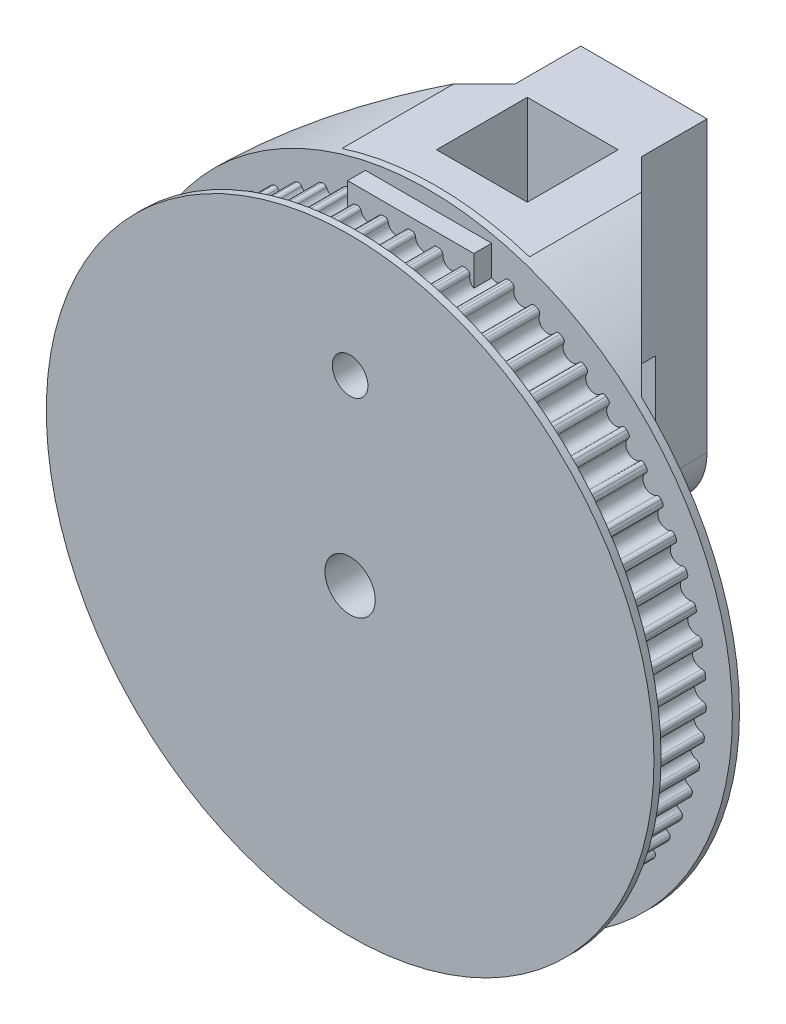
SolidWorks part; units mm, degrees
other "Markup1"
sketch "Sketch12" plane through (-30, -58, 49.7) normal (-0.8709, -0.4905, 0.0319) x (-0.1533, 0.2093, -0.9658)
other "Markup2"
sketch "Sketch14" plane through (30, -60, 49.7) normal (0.6168, -0.7172, 0.3243) x (-0.4689, -0.0038, 0.8832)
material "PETG"
ref_plane "Front Plane" through (0, 0, 0) normal (0, 0, 1) x (1, 0, 0)
ref_plane "Top Plane" through (0, 0, 0) normal (0, 1, 0) x (1, 0, 0)
ref_plane "Right Plane" through (0, 0, 0) normal (1, 0, 0) x (0, 0, -1)
sketch "Sketch1" plane through (0, 0, 0) normal (0, 1, 0) x (1, 0, 0)
  line L1 (-12.7375, -12.7375) -> (12.7375, -12.7375)
  line L2 (-12.7375, -12.7375) -> (-12.7375, 12.7375)
  line L3 (-12.7375, 12.7375) -> (12.7375, 12.7375)
  line L4 (12.7375, -12.7375) -> (12.7375, 12.7375)
  line L5 (-17.7, -17.7) -> (17.7, -17.7)
  line L6 (-17.7, -17.7) -> (-17.7, 17.7)
  line L7 (-17.7, 17.7) -> (17.7, 17.7)
  line L8 (17.7, -17.7) -> (17.7, 17.7)
  point P8 (0, -17.7)
  point P9 (0, -12.7375)
  point P12 (-17.7, 0)
  point P13 (-12.7375, 0)
  dimension "D1" = 25.475
  dimension "D2" = 35.4
extrude "Boss-Extrude1" add sketch "Sketch1" along normal blind 47.0375
extrude "Boss-Extrude2" add sketch "Sketch1<3>" against normal blind 14.9625 contours L1 L4 L3 L2 | L5 L8 L7 L6 L4 L1 L2 L3 region at (0, 0, 0) region at (-17.1994, 0, 0)
sketch "Sketch1<3>" plane through (0, 0, 0) normal (0, 1, 0) x (1, 0, 0) same geometry as "Sketch1"
sketch "Sketch3" plane through (0, 0, 0) normal (0, -1, 0) x (-1, 0, 0)
  circle A0 centre (0, 0) radius 3.15
  dimension "D1" = 6.3
extrude "Cut-Extrude1" cut sketch "Sketch3" along normal through all
sketch "Sketch13" plane through (0, -14.9625, 0) normal (0, -1, 0) x (1, 0, 0)
  circle A0 centre (0, 0) radius 5.5
  dimension "D1" = 11
extrude "Cut-Extrude4" cut sketch "Sketch13" against normal offset from surface (6.9625 mm away) 8 up to face at (0, 0, -3.15)
sketch "Sketch4" plane through (0, 0, 17.7) normal (0, 0, 1) x (1, 0, 0)
  line L0 (17.7, 47.0375) -> (17.7, -14.9625) construction
  line L1 (-17.7, 47.0375) -> (-17.7, -14.9625) construction
  line L2 (17.7, -34.0125) -> (17.7, -14.9625)
  line L3 (-17.7, -34.0125) -> (-17.7, -14.9625)
  line L5 (17.7, 47.0375) -> (-17.7, 47.0375)
  line L6 (17.7, 47.0375) -> (17.7, -14.9625)
  line L8 (-17.7, 47.0375) -> (-17.7, -14.9625)
  line L9 (-17.7, -14.9625) -> (17.7, -14.9625) construction
  line L10 (-17.7, 47.0375) -> (17.7, 47.0375) construction
  arc A0 (-17.7, -34.0125) -> (17.7, -34.0125) centre (0, -34.0125) ccw
  circle A1 centre (0, -34.0125) radius 7.05
  dimension "D2" = 14.1
  dimension "D1" = 19.05
extrude "Boss-Extrude3" add sketch "Sketch4" along normal blind 15
sketch "Sketch6" plane through (0, 0, 17.7) normal (0, 0, -1) x (-1, 0, 0)
  line L0 (17.7, -34.0125) -> (17.7, -14.9625)
  line L1 (17.7, -14.9625) -> (-17.7, -14.9625)
  line L2 (-17.7, -14.9625) -> (-17.7, -34.0125)
  arc A0 (-17.7, -34.0125) -> (17.7, -34.0125) centre (0, -34.0125) ccw
  arc A4 (-17.7, -34.0125) -> (17.7, -34.0125) centre (0, -34.0125) ccw construction
extrude "Cut-Extrude2" cut sketch "Sketch6" against normal blind 0.5375
sketch "Sketch7" plane through (0, 0, 18.2375) normal (0, 0, -1) x (-1, 0, 0)
  circle A0 centre (0, -34.0125) radius 11.0375
  arc A1 (-17.7, -34.0125) -> (17.7, -34.0125) centre (0, -34.0125) ccw construction
  dimension "D1" = 22.075
extrude "Cut-Extrude3" cut sketch "Sketch7" against normal blind 7
mirror "Mirror1" about plane through (0, 0, 0) normal (0, 0, 1) of "Boss-Extrude3", "Cut-Extrude2", "Cut-Extrude1", "Cut-Extrude3"
sketch "Sketch18" plane through (0, 0, 0) normal (0, 0, 1) x (1, 0, 0)
  line L0 (0, -13.5166) -> (-17.7, -3.2975)
  line L1 (-17.7, -3.2975) -> (-35.45, -34.0414) construction
  line L2 (-35.45, -34.0414) -> (-8.875, -49.3845) construction
  line L3 (-17.7, 47.0375) -> (-17.7, -34.0125) construction
  line L4 (0, -35.0322) -> (0, -50035.0322) construction
  line L5 (-17.7, -3.2975) -> (-17.7, -14.9625)
  line L6 (17.7, -34.0125) -> (17.7, 47.0375) construction
  line L7 (17.7, -3.2975) -> (0, -13.5166)
  line L10 (17.7, -14.9625) -> (17.7, -3.2975)
  line L11 (-17.7, -14.9625) -> (17.7, -14.9625)
  line L12 (-5.5, -14.9625) -> (5.5, -14.9625) construction
  circle A0 centre (0, -34.0125) radius 17.75 construction
  arc A2 (-17.7, -34.0125) -> (17.7, -34.0125) centre (0, -34.0125) ccw construction
  dimension "D2" = 120
  dimension "D1" = 35.5
extrude "Cut-Extrude10" cut sketch "Sketch18" along normal up to surface and the other way up to surface up to face at (-11.0375, -34.0125, 18.2375) other way up to face at (-11.0375, -34.0125, -18.2375)
ref_plane "Plane1" through (0, 0, 27.7) normal (0, 0, 1) x (1, 0, 0)
sketch "Sketch9" plane through (0, 0, 27.7) normal (0, 0, 1) x (1, 0, 0)
  circle A0 centre (0, -34.0125) radius 85.2141
  circle A1 centre (0, -34.0125) radius 7.05 construction
  circle A2 centre (0, -34.0125) radius 7.05
  dimension "D1" = 170.4282
extrude "Boss-Extrude4" add sketch "Sketch9" against normal blind 2 contours A0 region at (-82.8039, -34.0125, 27.7)
sketch "Sketch10" plane through (0, 0, 27.7) normal (0, 0, -1) x (-1, 0, 0)
  line L0 (0, -41.0625) -> (0, -50041.0625) construction
  line L1 (0, -34.0125) -> (-3.9983, -114.1269) construction
  line L2 (0, -34.0125) -> (3.9983, -114.1269) construction
  circle A0 centre (0, -34.0125) radius 80.2141 construction
  circle A1 centre (0, -34.0125) radius 7.05
  circle A2 centre (0, -34.0125) radius 85.2141 construction
  circle A3 centre (0, -34.0125) radius 7.05 construction
  arc A4 (2.4815, -110.9206) -> (-2.4815, -110.9206) centre (0, -111.1266) ccw
  arc A5 (-3.5233, -111.8369) -> (-2.4815, -110.9206) centre (-3.478, -110.8379) ccw
  circle A6 centre (0, -34.0125) radius 77.9041 construction
  arc A7 (2.4815, -110.9206) -> (3.5233, -111.8369) centre (3.478, -110.8379) ccw
  arc A8 (3.5233, -111.8369) -> (3.8832, -111.8198) centre (0, -34.0125) ccw
  arc A9 (-3.8832, -111.8198) -> (-3.5233, -111.8369) centre (0, -34.0125) ccw
  arc A10 (-11.611, -111.0465) -> (-11.2546, -111.0993) centre (0, -34.0125) ccw
  arc A11 (-11.2546, -111.0993) -> (-10.1267, -110.2914) centre (-11.1101, -110.1098) ccw
  arc A12 (-5.1884, -110.7855) -> (-10.1267, -110.2914) centre (-7.6781, -110.7434) ccw
  arc A13 (-5.1884, -110.7855) -> (-4.243, -111.801) centre (-4.1886, -110.8024) ccw
  arc A14 (-4.243, -111.801) -> (-3.8832, -111.8198) centre (0, -34.0125) ccw
  arc A15 (-19.2234, -109.5076) -> (-18.874, -109.5957) centre (0, -34.0125) ccw
  arc A16 (-18.874, -109.5957) -> (-17.6713, -108.904) centre (-18.6317, -108.6255) ccw
  arc A17 (-12.8068, -109.8874) -> (-17.6713, -108.904) centre (-15.2799, -109.5976) ccw
  arc A18 (-12.8068, -109.8874) -> (-11.9672, -110.9919) centre (-11.8136, -110.0038) ccw
  arc A19 (-11.9672, -110.9919) -> (-11.611, -111.0465) centre (0, -34.0125) ccw
  arc A20 (-26.6448, -107.2184) -> (-26.3059, -107.3409) centre (0, -34.0125) ccw
  arc A21 (-26.3059, -107.3409) -> (-25.0403, -106.7724) centre (-25.9682, -106.3996) ccw
  arc A22 (-20.2978, -108.2352) -> (-25.0403, -106.7724) centre (-22.7298, -107.7006) ccw
  arc A23 (-20.2978, -108.2352) -> (-19.5724, -109.4179) centre (-19.3212, -108.4499) ccw
  arc A24 (-19.5724, -109.4179) -> (-19.2234, -109.5076) centre (0, -34.0125) ccw
  arc A25 (-33.8013, -104.2017) -> (-33.4763, -104.3573) centre (0, -34.0125) ccw
  arc A26 (-33.4763, -104.3573) -> (-32.1604, -103.9176) centre (-33.0466, -103.4543) ccw
  arc A27 (-27.5872, -105.8454) -> (-32.1604, -103.9176) centre (-29.9538, -105.0713) ccw
  arc A28 (-27.5872, -105.8454) -> (-26.9831, -107.0944) centre (-26.6367, -106.1563) ccw
  arc A29 (-26.9831, -107.0944) -> (-26.6448, -107.2184) centre (0, -34.0125) ccw
  arc A30 (-40.6219, -100.4874) -> (-40.314, -100.6745) centre (0, -34.0125) ccw
  arc A31 (-40.314, -100.6745) -> (-38.9609, -100.3681) centre (-39.7965, -99.8188) ccw
  arc A32 (-34.6023, -102.7416) -> (-38.9609, -100.3681) centre (-36.8801, -101.7358) ccw
  arc A33 (-34.6023, -102.7416) -> (-34.1256, -104.0446) centre (-33.6876, -103.1456) ccw
  arc A34 (-34.1256, -104.0446) -> (-33.8013, -104.2017) centre (0, -34.0125) ccw
  arc A35 (-47.0388, -96.1124) -> (-46.7511, -96.3293) centre (0, -34.0125) ccw
  arc A36 (-46.7511, -96.3293) -> (-45.3742, -96.1591) centre (-46.151, -95.5294) ccw
  arc A37 (-41.2736, -98.9548) -> (-45.3742, -96.1591) centre (-43.4399, -97.7272) ccw
  arc A38 (-41.2736, -98.9548) -> (-40.929, -100.2987) centre (-40.4036, -99.4479) ccw
  arc A39 (-40.929, -100.2987) -> (-40.6219, -100.4874) centre (0, -34.0125) ccw
  arc A40 (-52.9882, -91.1202) -> (-52.7235, -91.3647) centre (0, -34.0125) ccw
  arc A41 (-52.7235, -91.3647) -> (-51.3365, -91.3325) centre (-52.0467, -90.6285) ccw
  arc A42 (-47.5347, -94.5226) -> (-51.3365, -91.3325) centre (-49.568, -93.0853) ccw
  arc A43 (-47.5347, -94.5226) -> (-47.3256, -95.8941) centre (-46.7181, -95.0998) ccw
  arc A44 (-47.3256, -95.8941) -> (-47.0388, -96.1124) centre (0, -34.0125) ccw
  arc A45 (-58.411, -85.5605) -> (-58.172, -85.8302) centre (0, -34.0125) ccw
  arc A46 (-58.172, -85.8302) -> (-56.7886, -85.9362) centre (-57.4253, -85.165) ccw
  arc A47 (-53.3233, -89.489) -> (-56.7886, -85.9362) centre (-55.2034, -87.8564) ccw
  arc A48 (-53.3233, -89.489) -> (-53.2518, -90.8745) centre (-52.5683, -90.1446) ccw
  arc A49 (-53.2518, -90.8745) -> (-52.9882, -91.1202) centre (0, -34.0125) ccw
  arc A50 (-63.2533, -79.4885) -> (-63.0423, -79.7806) centre (0, -34.0125) ccw
  arc A51 (-63.0423, -79.7806) -> (-61.6764, -80.0238) centre (-62.233, -79.1931) ccw
  arc A52 (-58.582, -83.904) -> (-61.6764, -80.0238) centre (-60.2902, -82.0923) ccw
  arc A53 (-58.582, -83.904) -> (-58.6488, -85.2898) centre (-57.896, -84.6316) ccw
  arc A54 (-58.6488, -85.2898) -> (-58.411, -85.5605) centre (0, -34.0125) ccw
  arc A55 (-67.4669, -72.9645) -> (-67.286, -73.2762) centre (0, -34.0125) ccw
  arc A56 (-67.286, -73.2762) -> (-65.9511, -73.6542) centre (-66.4223, -72.7722) ccw
  arc A57 (-63.2585, -77.8232) -> (-65.9511, -73.6542) centre (-64.7778, -75.8505) ccw
  arc A58 (-63.2585, -77.8232) -> (-63.463, -79.1955) centre (-62.6483, -78.6155) ccw
  arc A59 (-63.463, -79.1955) -> (-63.2533, -79.4885) centre (0, -34.0125) ccw
  arc A60 (-71.01, -66.0534) -> (-70.8611, -66.3816) centre (0, -34.0125) ccw
  arc A61 (-70.8611, -66.3816) -> (-69.5704, -66.8906) centre (-69.9515, -65.9661) ccw
  arc A62 (-67.3063, -71.307) -> (-69.5704, -66.8906) centre (-68.6217, -69.1928) ccw
  arc A63 (-67.3063, -71.307) -> (-67.6464, -72.6521) centre (-66.778, -72.1561) ccw
  arc A64 (-67.6464, -72.6521) -> (-67.4669, -72.9645) centre (0, -34.0125) ccw
  arc A65 (-73.8474, -58.8239) -> (-73.7319, -59.1652) centre (0, -34.0125) ccw
  arc A66 (-73.7319, -59.1652) -> (-72.4983, -59.8003) centre (-72.7854, -58.8424) ccw
  arc A67 (-70.6852, -64.4201) -> (-72.4983, -59.8003) centre (-71.7835, -62.1854) ccw
  arc A68 (-70.6852, -64.4201) -> (-71.1575, -65.7247) centre (-70.2441, -65.3176) ccw
  arc A69 (-71.1575, -65.7247) -> (-71.01, -66.0534) centre (0, -34.0125) ccw
  arc A70 (-75.9509, -51.3478) -> (-75.8699, -51.6989) centre (0, -34.0125) ccw
  arc A71 (-75.8699, -51.6989) -> (-74.7057, -52.4536) centre (-74.896, -51.4719) ccw
  arc A72 (-73.3615, -57.2311) -> (-74.7057, -52.4536) centre (-74.2319, -54.8981) ccw
  arc A73 (-73.3615, -57.2311) -> (-73.9614, -58.4821) centre (-73.012, -58.168) ccw
  arc A74 (-73.9614, -58.4821) -> (-73.8474, -58.8239) centre (0, -34.0125) ccw
  arc A75 (-77.2995, -43.6994) -> (-77.2539, -44.0568) centre (0, -34.0125) ccw
  arc A76 (-77.2539, -44.0568) -> (-76.1706, -44.9237) centre (-76.2622, -43.9279) ccw
  arc A77 (-75.3088, -49.8112) -> (-76.1706, -44.9237) centre (-75.9426, -47.4032) ccw
  arc A78 (-75.3088, -49.8112) -> (-76.0302, -50.9963) centre (-75.0543, -50.7783) ccw
  arc A79 (-76.0302, -50.9963) -> (-75.9509, -51.3478) centre (0, -34.0125) ccw
  arc A80 (-77.8799, -35.9547) -> (-77.8701, -36.3149) centre (0, -34.0125) ccw
  arc A81 (-77.8701, -36.3149) -> (-76.8785, -37.2853) centre (-76.8705, -36.2854) ccw
  arc A82 (-76.5076, -42.2344) -> (-76.8785, -37.2853) centre (-76.8985, -39.7752) ccw
  arc A83 (-76.5076, -42.2344) -> (-77.3435, -43.3417) centre (-76.3507, -43.222) ccw
  arc A84 (-77.3435, -43.3417) -> (-77.2995, -43.6994) centre (0, -34.0125) ccw
  arc A85 (-77.6863, -28.1907) -> (-77.7124, -28.5501) centre (0, -34.0125) ccw
  arc A86 (-77.7124, -28.5501) -> (-76.8224, -29.6144) centre (-76.7148, -28.6202) ccw
  arc A87 (-76.9461, -34.5758) -> (-76.8224, -29.6144) centre (-77.0901, -32.09) ccw
  arc A88 (-76.9461, -34.5758) -> (-77.888, -35.5945) centre (-76.8882, -35.5741) ccw
  arc A89 (-77.888, -35.5945) -> (-77.8799, -35.9547) centre (0, -34.0125) ccw
  arc A90 (-76.7206, -20.4846) -> (-76.7823, -20.8396) centre (0, -34.0125) ccw
  arc A91 (-76.7823, -20.8396) -> (-76.0027, -21.9873) centre (-75.7967, -21.0087) ccw
  arc A92 (-76.6198, -26.9117) -> (-76.0027, -21.9873) centre (-76.5156, -24.4238) ccw
  arc A93 (-76.6198, -26.9117) -> (-77.6585, -27.8315) centre (-76.6616, -27.9108) ccw
  arc A94 (-77.6585, -27.8315) -> (-77.6863, -28.1907) centre (0, -34.0125) ccw
  arc A95 (-74.9924, -12.9129) -> (-75.0892, -13.26) centre (0, -34.0125) ccw
  arc A96 (-75.0892, -13.26) -> (-74.4277, -14.4796) centre (-74.1253, -13.5264) ccw
  arc A97 (-75.5321, -19.3181) -> (-74.4277, -14.4796) centre (-75.1807, -16.853) ccw
  arc A98 (-75.5321, -19.3181) -> (-76.6572, -20.1299) centre (-75.6732, -20.3081) ccw
  arc A99 (-76.6572, -20.1299) -> (-76.7206, -20.4846) centre (0, -34.0125) ccw
  arc A100 (-72.5189, -5.5509) -> (-72.6497, -5.8867) centre (0, -34.0125) ccw
  arc A101 (-72.6497, -5.8867) -> (-72.113, -7.166) centre (-71.7172, -6.2477) ccw
  arc A102 (-73.6936, -11.8705) -> (-72.113, -7.166) centre (-73.0986, -9.4527) ccw
  arc A103 (-73.6936, -11.8705) -> (-74.894, -12.5663) centre (-73.9326, -12.8416) ccw
  arc A104 (-74.894, -12.5663) -> (-74.9924, -12.9129) centre (0, -34.0125) ccw
  arc A105 (-69.3247, 1.5282) -> (-69.4883, 1.2071) centre (0, -34.0125) ccw
  arc A106 (-69.4883, 1.2071) -> (-69.0816, -0.1193) centre (-68.5963, 0.7551) ccw
  arc A107 (-71.1228, -4.6431) -> (-69.0816, -0.1193) centre (-70.2899, -2.2965) ccw
  arc A108 (-71.1228, -4.6431) -> (-72.3865, -5.2158) centre (-71.4573, -5.5855) ccw
  arc A109 (-72.3865, -5.2158) -> (-72.5189, -5.5509) centre (0, -34.0125) ccw
  arc A110 (-65.4415, 8.2541) -> (-65.6363, 7.9509) centre (0, -34.0125) ccw
  arc A111 (-65.6363, 7.9509) -> (-65.3637, 6.5906) centre (-64.7937, 7.4123) ccw
  arc A112 (-67.8451, 2.2925) -> (-65.3637, 6.5906) centre (-66.7828, 4.5445) ccw
  arc A113 (-67.8451, 2.2925) -> (-69.1595, 1.8485) centre (-68.2718, 1.3881) ccw
  arc A114 (-69.1595, 1.8485) -> (-69.3247, 1.5282) centre (0, -34.0125) ccw
  arc A115 (-60.9079, 14.5599) -> (-61.1319, 14.2777) centre (0, -34.0125) ccw
  arc A116 (-61.1319, 14.2777) -> (-60.9961, 12.8969) centre (-60.3472, 13.6578) ccw
  arc A117 (-63.8932, 8.8673) -> (-60.9961, 12.8969) centre (-62.6119, 11.0024) ccw
  arc A118 (-63.8932, 8.8673) -> (-65.2453, 8.5563) centre (-64.4077, 8.0099) ccw
  arc A119 (-65.2453, 8.5563) -> (-65.4415, 8.2541) centre (0, -34.0125) ccw
  arc A120 (-55.769, 20.383) -> (-56.02, 20.1245) centre (0, -34.0125) ccw
  arc A121 (-56.02, 20.1245) -> (-56.0223, 18.7371) centre (-55.3009, 19.4295) ccw
  arc A122 (-59.3062, 15.016) -> (-56.0223, 18.7371) centre (-57.8187, 17.0128) ccw
  arc A123 (-59.3062, 15.016) -> (-60.6826, 14.8411) centre (-59.9036, 14.214) ccw
  arc A124 (-60.6826, 14.8411) -> (-60.9079, 14.5599) centre (0, -34.0125) ccw
  arc A125 (-50.0758, 25.6655) -> (-50.3513, 25.4332) centre (0, -34.0125) ccw
  arc A126 (-50.3513, 25.4332) -> (-50.4918, 24.053) centre (-49.705, 24.6702) ccw
  arc A127 (-54.1299, 20.6773) -> (-50.4918, 24.053) centre (-52.4509, 22.5161) ccw
  arc A128 (-54.1299, 20.6773) -> (-55.5168, 20.6404) centre (-54.8041, 19.9388) ccw
  arc A129 (-55.5168, 20.6404) -> (-55.769, 20.383) centre (0, -34.0125) ccw
  arc A130 (-43.8849, 30.3549) -> (-44.1822, 30.1512) centre (0, -34.0125) ccw
  arc A131 (-44.1822, 30.1512) -> (-44.4594, 28.7918) centre (-43.6151, 29.3276) ccw
  arc A132 (-48.4155, 25.7951) -> (-44.4594, 28.7918) centre (-46.5618, 27.4576) ccw
  arc A133 (-48.4155, 25.7951) -> (-49.7992, 25.8965) centre (-49.16, 25.1275) ccw
  arc A134 (-49.7992, 25.8965) -> (-50.0758, 25.6655) centre (0, -34.0125) ccw
  arc A135 (-37.2579, 34.4046) -> (-37.574, 34.2315) centre (0, -34.0125) ccw
  arc A136 (-37.574, 34.2315) -> (-37.9852, 32.9064) centre (-37.0917, 33.3555) ccw
  arc A137 (-42.22, 30.3186) -> (-37.9852, 32.9064) centre (-40.21, 31.7883) ccw
  arc A138 (-42.22, 30.3186) -> (-43.5867, 30.5572) centre (-43.0272, 29.7283) ccw
  arc A139 (-43.5867, 30.5572) -> (-43.8849, 30.3549) centre (0, -34.0125) ccw
  arc A140 (-30.2607, 37.7743) -> (-30.5924, 37.6335) centre (0, -34.0125) ccw
  arc A141 (-30.5924, 37.6335) -> (-31.1335, 36.356) centre (-30.1997, 36.7139) ccw
  arc A142 (-35.6049, 34.2027) -> (-31.1335, 36.356) centre (-33.4586, 35.4649) ccw
  arc A143 (-35.6049, 34.2027) -> (-36.9411, 34.5762) centre (-36.4669, 33.6957) ccw
  arc A144 (-36.9411, 34.5762) -> (-37.2579, 34.4046) centre (0, -34.0125) ccw
  arc A145 (-22.9626, 40.4305) -> (-23.3067, 40.3235) centre (0, -34.0125) ccw
  arc A146 (-23.3067, 40.3235) -> (-23.9723, 39.1062) centre (-23.0075, 39.3693) ccw
  arc A147 (-28.6359, 37.4088) -> (-23.9723, 39.1062) centre (-26.3746, 38.451) ccw
  arc A148 (-28.6359, 37.4088) -> (-29.9283, 37.9135) centre (-29.5441, 36.9902) ccw
  arc A149 (-29.9283, 37.9135) -> (-30.2607, 37.7743) centre (0, -34.0125) ccw
  arc A150 (-15.4364, 42.3469) -> (-15.7894, 42.2747) centre (0, -34.0125) ccw
  arc A151 (-15.7894, 42.2747) -> (-16.5729, 41.1297) centre (-15.5867, 41.2955) ccw
  arc A152 (-21.3824, 39.9051) -> (-16.5729, 41.1297) centre (-19.0285, 40.717) ccw
  arc A153 (-21.3824, 39.9051) -> (-22.6181, 40.5359) centre (-22.3277, 39.579) ccw
  arc A154 (-22.6181, 40.5359) -> (-22.9626, 40.4305) centre (0, -34.0125) ccw
  arc A155 (-7.7567, 43.5045) -> (-8.1152, 43.4678) centre (0, -34.0125) ccw
  arc A156 (-8.1152, 43.4678) -> (-9.0088, 42.4065) centre (-8.011, 42.4732) ccw
  arc A157 (-13.9163, 41.6668) -> (-9.0088, 42.4065) centre (-11.4933, 42.2403) ccw
  arc A158 (-13.9163, 41.6668) -> (-15.083, 42.4175) centre (-14.8894, 41.4365) ccw
  arc A159 (-15.083, 42.4175) -> (-15.4364, 42.3469) centre (0, -34.0125) ccw
  arc A160 (0, 43.8916) -> (-0.3603, 43.8908) centre (0, -34.0125) ccw
  arc A161 (-0.3603, 43.8908) -> (-1.3552, 42.9237) centre (-0.3557, 42.8908) ccw
  arc A162 (-6.3119, 42.6763) -> (-1.3552, 42.9237) centre (-3.8438, 43.0057) ccw
  arc A163 (-6.3119, 42.6763) -> (-7.3981, 43.5395) centre (-7.3031, 42.544) ccw
  arc A164 (-7.3981, 43.5395) -> (-7.7567, 43.5045) centre (0, -34.0125) ccw
  arc A165 (7.7567, 43.5045) -> (7.3981, 43.5395) centre (0, -34.0125) ccw
  arc A166 (7.3981, 43.5395) -> (6.3119, 42.6763) centre (7.3031, 42.544) ccw
  arc A167 (1.3552, 42.9237) -> (6.3119, 42.6763) centre (3.8438, 43.0057) ccw
  arc A168 (1.3552, 42.9237) -> (0.3603, 43.8908) centre (0.3557, 42.8908) ccw
  arc A169 (0.3603, 43.8908) -> (0, 43.8916) centre (0, -34.0125) ccw
  arc A170 (15.4364, 42.3469) -> (15.083, 42.4175) centre (0, -34.0125) ccw
  arc A171 (15.083, 42.4175) -> (13.9163, 41.6668) centre (14.8894, 41.4365) ccw
  arc A172 (9.0088, 42.4065) -> (13.9163, 41.6668) centre (11.4933, 42.2403) ccw
  arc A173 (9.0088, 42.4065) -> (8.1152, 43.4678) centre (8.011, 42.4732) ccw
  arc A174 (8.1152, 43.4678) -> (7.7567, 43.5045) centre (0, -34.0125) ccw
  arc A175 (22.9626, 40.4305) -> (22.6181, 40.5359) centre (0, -34.0125) ccw
  arc A176 (22.6181, 40.5359) -> (21.3824, 39.9051) centre (22.3277, 39.579) ccw
  arc A177 (16.5729, 41.1297) -> (21.3824, 39.9051) centre (19.0285, 40.717) ccw
  arc A178 (16.5729, 41.1297) -> (15.7894, 42.2747) centre (15.5867, 41.2955) ccw
  arc A179 (15.7894, 42.2747) -> (15.4364, 42.3469) centre (0, -34.0125) ccw
  arc A180 (30.2607, 37.7743) -> (29.9283, 37.9135) centre (0, -34.0125) ccw
  arc A181 (29.9283, 37.9135) -> (28.6359, 37.4088) centre (29.5441, 36.9902) ccw
  arc A182 (23.9723, 39.1062) -> (28.6359, 37.4088) centre (26.3746, 38.451) ccw
  arc A183 (23.9723, 39.1062) -> (23.3067, 40.3235) centre (23.0075, 39.3693) ccw
  arc A184 (23.3067, 40.3235) -> (22.9626, 40.4305) centre (0, -34.0125) ccw
  arc A185 (37.2579, 34.4046) -> (36.9411, 34.5762) centre (0, -34.0125) ccw
  arc A186 (36.9411, 34.5762) -> (35.6049, 34.2027) centre (36.4669, 33.6957) ccw
  arc A187 (31.1335, 36.356) -> (35.6049, 34.2027) centre (33.4586, 35.4649) ccw
  arc A188 (31.1335, 36.356) -> (30.5924, 37.6335) centre (30.1997, 36.7139) ccw
  arc A189 (30.5924, 37.6335) -> (30.2607, 37.7743) centre (0, -34.0125) ccw
  arc A190 (43.8849, 30.3549) -> (43.5867, 30.5572) centre (0, -34.0125) ccw
  arc A191 (43.5867, 30.5572) -> (42.22, 30.3186) centre (43.0272, 29.7283) ccw
  arc A192 (37.9852, 32.9064) -> (42.22, 30.3186) centre (40.21, 31.7883) ccw
  arc A193 (37.9852, 32.9064) -> (37.574, 34.2315) centre (37.0917, 33.3555) ccw
  arc A194 (37.574, 34.2315) -> (37.2579, 34.4046) centre (0, -34.0125) ccw
  arc A195 (50.0758, 25.6655) -> (49.7992, 25.8965) centre (0, -34.0125) ccw
  arc A196 (49.7992, 25.8965) -> (48.4155, 25.7951) centre (49.16, 25.1275) ccw
  arc A197 (44.4594, 28.7918) -> (48.4155, 25.7951) centre (46.5618, 27.4576) ccw
  arc A198 (44.4594, 28.7918) -> (44.1822, 30.1512) centre (43.6151, 29.3276) ccw
  arc A199 (44.1822, 30.1512) -> (43.8849, 30.3549) centre (0, -34.0125) ccw
  arc A200 (55.769, 20.383) -> (55.5168, 20.6404) centre (0, -34.0125) ccw
  arc A201 (55.5168, 20.6404) -> (54.1299, 20.6773) centre (54.8041, 19.9388) ccw
  arc A202 (50.4918, 24.053) -> (54.1299, 20.6773) centre (52.4509, 22.5161) ccw
  arc A203 (50.4918, 24.053) -> (50.3513, 25.4332) centre (49.705, 24.6702) ccw
  arc A204 (50.3513, 25.4332) -> (50.0758, 25.6655) centre (0, -34.0125) ccw
  arc A205 (60.9079, 14.5599) -> (60.6826, 14.8411) centre (0, -34.0125) ccw
  arc A206 (60.6826, 14.8411) -> (59.3062, 15.016) centre (59.9036, 14.214) ccw
  arc A207 (56.0223, 18.7371) -> (59.3062, 15.016) centre (57.8187, 17.0128) ccw
  arc A208 (56.0223, 18.7371) -> (56.02, 20.1245) centre (55.3009, 19.4295) ccw
  arc A209 (56.02, 20.1245) -> (55.769, 20.383) centre (0, -34.0125) ccw
  arc A210 (65.4415, 8.2541) -> (65.2453, 8.5563) centre (0, -34.0125) ccw
  arc A211 (65.2453, 8.5563) -> (63.8932, 8.8673) centre (64.4077, 8.0099) ccw
  arc A212 (60.9961, 12.8969) -> (63.8932, 8.8673) centre (62.6119, 11.0024) ccw
  arc A213 (60.9961, 12.8969) -> (61.1319, 14.2777) centre (60.3472, 13.6578) ccw
  arc A214 (61.1319, 14.2777) -> (60.9079, 14.5599) centre (0, -34.0125) ccw
  arc A215 (69.3247, 1.5282) -> (69.1595, 1.8485) centre (0, -34.0125) ccw
  arc A216 (69.1595, 1.8485) -> (67.8451, 2.2925) centre (68.2718, 1.3881) ccw
  arc A217 (65.3637, 6.5906) -> (67.8451, 2.2925) centre (66.7828, 4.5445) ccw
  arc A218 (65.3637, 6.5906) -> (65.6363, 7.9509) centre (64.7937, 7.4123) ccw
  arc A219 (65.6363, 7.9509) -> (65.4415, 8.2541) centre (0, -34.0125) ccw
  arc A220 (72.5189, -5.5509) -> (72.3865, -5.2158) centre (0, -34.0125) ccw
  arc A221 (72.3865, -5.2158) -> (71.1228, -4.6431) centre (71.4573, -5.5855) ccw
  arc A222 (69.0816, -0.1193) -> (71.1228, -4.6431) centre (70.2899, -2.2965) ccw
  arc A223 (69.0816, -0.1193) -> (69.4883, 1.2071) centre (68.5963, 0.7551) ccw
  arc A224 (69.4883, 1.2071) -> (69.3247, 1.5282) centre (0, -34.0125) ccw
  arc A225 (74.9924, -12.9129) -> (74.894, -12.5663) centre (0, -34.0125) ccw
  arc A226 (74.894, -12.5663) -> (73.6936, -11.8705) centre (73.9326, -12.8416) ccw
  arc A227 (72.113, -7.166) -> (73.6936, -11.8705) centre (73.0986, -9.4527) ccw
  arc A228 (72.113, -7.166) -> (72.6497, -5.8867) centre (71.7172, -6.2477) ccw
  arc A229 (72.6497, -5.8867) -> (72.5189, -5.5509) centre (0, -34.0125) ccw
  arc A230 (76.7206, -20.4846) -> (76.6572, -20.1299) centre (0, -34.0125) ccw
  arc A231 (76.6572, -20.1299) -> (75.5321, -19.3181) centre (75.6732, -20.3081) ccw
  arc A232 (74.4277, -14.4796) -> (75.5321, -19.3181) centre (75.1807, -16.853) ccw
  arc A233 (74.4277, -14.4796) -> (75.0892, -13.26) centre (74.1253, -13.5264) ccw
  arc A234 (75.0892, -13.26) -> (74.9924, -12.9129) centre (0, -34.0125) ccw
  arc A235 (77.6863, -28.1907) -> (77.6585, -27.8315) centre (0, -34.0125) ccw
  arc A236 (77.6585, -27.8315) -> (76.6198, -26.9117) centre (76.6616, -27.9108) ccw
  arc A237 (76.0027, -21.9873) -> (76.6198, -26.9117) centre (76.5156, -24.4238) ccw
  arc A238 (76.0027, -21.9873) -> (76.7823, -20.8396) centre (75.7967, -21.0087) ccw
  arc A239 (76.7823, -20.8396) -> (76.7206, -20.4846) centre (0, -34.0125) ccw
  arc A240 (77.8799, -35.9547) -> (77.888, -35.5945) centre (0, -34.0125) ccw
  arc A241 (77.888, -35.5945) -> (76.9461, -34.5758) centre (76.8882, -35.5741) ccw
  arc A242 (76.8224, -29.6144) -> (76.9461, -34.5758) centre (77.0901, -32.09) ccw
  arc A243 (76.8224, -29.6144) -> (77.7124, -28.5501) centre (76.7148, -28.6202) ccw
  arc A244 (77.7124, -28.5501) -> (77.6863, -28.1907) centre (0, -34.0125) ccw
  arc A245 (77.2995, -43.6994) -> (77.3435, -43.3417) centre (0, -34.0125) ccw
  arc A246 (77.3435, -43.3417) -> (76.5076, -42.2344) centre (76.3507, -43.222) ccw
  arc A247 (76.8785, -37.2853) -> (76.5076, -42.2344) centre (76.8985, -39.7752) ccw
  arc A248 (76.8785, -37.2853) -> (77.8701, -36.3149) centre (76.8705, -36.2854) ccw
  arc A249 (77.8701, -36.3149) -> (77.8799, -35.9547) centre (0, -34.0125) ccw
  arc A250 (75.9509, -51.3478) -> (76.0302, -50.9963) centre (0, -34.0125) ccw
  arc A251 (76.0302, -50.9963) -> (75.3088, -49.8112) centre (75.0543, -50.7783) ccw
  arc A252 (76.1706, -44.9237) -> (75.3088, -49.8112) centre (75.9426, -47.4032) ccw
  arc A253 (76.1706, -44.9237) -> (77.2539, -44.0568) centre (76.2622, -43.9279) ccw
  arc A254 (77.2539, -44.0568) -> (77.2995, -43.6994) centre (0, -34.0125) ccw
  arc A255 (73.8474, -58.8239) -> (73.9614, -58.4821) centre (0, -34.0125) ccw
  arc A256 (73.9614, -58.4821) -> (73.3615, -57.2311) centre (73.012, -58.168) ccw
  arc A257 (74.7057, -52.4536) -> (73.3615, -57.2311) centre (74.2319, -54.8981) ccw
  arc A258 (74.7057, -52.4536) -> (75.8699, -51.6989) centre (74.896, -51.4719) ccw
  arc A259 (75.8699, -51.6989) -> (75.9509, -51.3478) centre (0, -34.0125) ccw
  arc A260 (71.01, -66.0534) -> (71.1575, -65.7247) centre (0, -34.0125) ccw
  arc A261 (71.1575, -65.7247) -> (70.6852, -64.4201) centre (70.2441, -65.3176) ccw
  arc A262 (72.4983, -59.8003) -> (70.6852, -64.4201) centre (71.7835, -62.1854) ccw
  arc A263 (72.4983, -59.8003) -> (73.7319, -59.1652) centre (72.7854, -58.8424) ccw
  arc A264 (73.7319, -59.1652) -> (73.8474, -58.8239) centre (0, -34.0125) ccw
  arc A265 (67.4669, -72.9645) -> (67.6464, -72.6521) centre (0, -34.0125) ccw
  arc A266 (67.6464, -72.6521) -> (67.3063, -71.307) centre (66.778, -72.1561) ccw
  arc A267 (69.5704, -66.8906) -> (67.3063, -71.307) centre (68.6217, -69.1928) ccw
  arc A268 (69.5704, -66.8906) -> (70.8611, -66.3816) centre (69.9515, -65.9661) ccw
  arc A269 (70.8611, -66.3816) -> (71.01, -66.0534) centre (0, -34.0125) ccw
  arc A270 (63.2533, -79.4885) -> (63.463, -79.1955) centre (0, -34.0125) ccw
  arc A271 (63.463, -79.1955) -> (63.2585, -77.8232) centre (62.6483, -78.6155) ccw
  arc A272 (65.9511, -73.6542) -> (63.2585, -77.8232) centre (64.7778, -75.8505) ccw
  arc A273 (65.9511, -73.6542) -> (67.286, -73.2762) centre (66.4223, -72.7722) ccw
  arc A274 (67.286, -73.2762) -> (67.4669, -72.9645) centre (0, -34.0125) ccw
  arc A275 (58.411, -85.5605) -> (58.6488, -85.2898) centre (0, -34.0125) ccw
  arc A276 (58.6488, -85.2898) -> (58.582, -83.904) centre (57.896, -84.6316) ccw
  arc A277 (61.6764, -80.0238) -> (58.582, -83.904) centre (60.2902, -82.0923) ccw
  arc A278 (61.6764, -80.0238) -> (63.0423, -79.7806) centre (62.233, -79.1931) ccw
  arc A279 (63.0423, -79.7806) -> (63.2533, -79.4885) centre (0, -34.0125) ccw
  arc A280 (52.9882, -91.1202) -> (53.2518, -90.8745) centre (0, -34.0125) ccw
  arc A281 (53.2518, -90.8745) -> (53.3233, -89.489) centre (52.5683, -90.1446) ccw
  arc A282 (56.7886, -85.9362) -> (53.3233, -89.489) centre (55.2034, -87.8564) ccw
  arc A283 (56.7886, -85.9362) -> (58.172, -85.8302) centre (57.4253, -85.165) ccw
  arc A284 (58.172, -85.8302) -> (58.411, -85.5605) centre (0, -34.0125) ccw
  arc A285 (47.0388, -96.1124) -> (47.3256, -95.8941) centre (0, -34.0125) ccw
  arc A286 (47.3256, -95.8941) -> (47.5347, -94.5226) centre (46.7181, -95.0998) ccw
  arc A287 (51.3365, -91.3325) -> (47.5347, -94.5226) centre (49.568, -93.0853) ccw
  arc A288 (51.3365, -91.3325) -> (52.7235, -91.3647) centre (52.0467, -90.6285) ccw
  arc A289 (52.7235, -91.3647) -> (52.9882, -91.1202) centre (0, -34.0125) ccw
  arc A290 (40.6219, -100.4874) -> (40.929, -100.2987) centre (0, -34.0125) ccw
  arc A291 (40.929, -100.2987) -> (41.2736, -98.9548) centre (40.4036, -99.4479) ccw
  arc A292 (45.3742, -96.1591) -> (41.2736, -98.9548) centre (43.4399, -97.7272) ccw
  arc A293 (45.3742, -96.1591) -> (46.7511, -96.3293) centre (46.151, -95.5294) ccw
  arc A294 (46.7511, -96.3293) -> (47.0388, -96.1124) centre (0, -34.0125) ccw
  arc A295 (33.8013, -104.2017) -> (34.1256, -104.0446) centre (0, -34.0125) ccw
  arc A296 (34.1256, -104.0446) -> (34.6023, -102.7416) centre (33.6876, -103.1456) ccw
  arc A297 (38.9609, -100.3681) -> (34.6023, -102.7416) centre (36.8801, -101.7358) ccw
  arc A298 (38.9609, -100.3681) -> (40.314, -100.6745) centre (39.7965, -99.8188) ccw
  arc A299 (40.314, -100.6745) -> (40.6219, -100.4874) centre (0, -34.0125) ccw
  arc A300 (26.6448, -107.2184) -> (26.9831, -107.0944) centre (0, -34.0125) ccw
  arc A301 (26.9831, -107.0944) -> (27.5872, -105.8454) centre (26.6367, -106.1563) ccw
  arc A302 (32.1604, -103.9176) -> (27.5872, -105.8454) centre (29.9538, -105.0713) ccw
  arc A303 (32.1604, -103.9176) -> (33.4763, -104.3573) centre (33.0466, -103.4543) ccw
  arc A304 (33.4763, -104.3573) -> (33.8013, -104.2017) centre (0, -34.0125) ccw
  arc A305 (19.2234, -109.5076) -> (19.5724, -109.4179) centre (0, -34.0125) ccw
  arc A306 (19.5724, -109.4179) -> (20.2978, -108.2352) centre (19.3212, -108.4499) ccw
  arc A307 (25.0403, -106.7724) -> (20.2978, -108.2352) centre (22.7298, -107.7006) ccw
  arc A308 (25.0403, -106.7724) -> (26.3059, -107.3409) centre (25.9682, -106.3996) ccw
  arc A309 (26.3059, -107.3409) -> (26.6448, -107.2184) centre (0, -34.0125) ccw
  arc A310 (11.611, -111.0465) -> (11.9672, -110.9919) centre (0, -34.0125) ccw
  arc A311 (11.9672, -110.9919) -> (12.8068, -109.8874) centre (11.8136, -110.0038) ccw
  arc A312 (17.6713, -108.904) -> (12.8068, -109.8874) centre (15.2799, -109.5976) ccw
  arc A313 (17.6713, -108.904) -> (18.874, -109.5957) centre (18.6317, -108.6255) ccw
  arc A314 (18.874, -109.5957) -> (19.2234, -109.5076) centre (0, -34.0125) ccw
  arc A315 (3.8832, -111.8198) -> (4.243, -111.801) centre (0, -34.0125) ccw
  arc A316 (4.243, -111.801) -> (5.1884, -110.7855) centre (4.1886, -110.8024) ccw
  arc A317 (10.1267, -110.2914) -> (5.1884, -110.7855) centre (7.6781, -110.7434) ccw
  arc A318 (10.1267, -110.2914) -> (11.2546, -111.0993) centre (11.1101, -110.1098) ccw
  arc A319 (11.2546, -111.0993) -> (11.611, -111.0465) centre (0, -34.0125) ccw
  point P10 (0, -108.6366)
  point P14 (0, -111.9166)
  point P27 (0, -114.2266)
  arc M13 (-17.7, -34.0125) -> (17.7, -34.0125) centre (0, -34.0125) ccw
  line M14 (17.7, -34.0125) -> (17.7, 47.0375)
  line M16 (-17.7, 47.0375) -> (-17.7, -34.0125)
  dimension "D1" = 160.4282
  dimension "D2" = 2.49
  dimension "D3" = 1
  dimension "D4" = 3.28
  dimension "D6" = 5.59
  dimension "D5" = 8
  dimension "D7" = 63
extrude "Boss-Extrude5" add sketch "Sketch10" against normal blind 20 contours A8 A7 A4 A5 A9 A14 A13 A12 A11 A10 A19 A18 A17 A16 A15 A24 A23 A22 A21 A20 A29 A28 A27 A26 A25 A34 A33 A32 A31 A30 A39 A38 A37 A36 A35 A44 A43 A42 A41 A40 A49 A48 A47 A46 A45 A54 | A179 A178 A177 A152 A151 A150 A159 A158 A157 A156 A155 A164 A163 A162 A161 A160 A169 A168 A167 A166 A165 A174 A173 A172 A171 A170 A1 M14 M13 M16 region at (0, -106.4572, 27.7) region at (0, -1.7178, 27.7)
sketch "Sketch11" plane through (0, 0, 47.7) normal (0, 0, 1) x (1, 0, 0)
  circle A0 centre (0, -34.0125) radius 85.2141
  circle A1 centre (0, -34.0125) radius 7.05
  circle A3 centre (0, -34.0125) radius 85.2141 construction
  circle A4 centre (0, -34.0125) radius 7.05 construction
extrude "Boss-Extrude6" add sketch "Sketch11" along normal blind 2 contours A0 region at (-82.8039, -34.0125, 47.7)
sketch "Sketch15" plane through (0, 0, -32.7) normal (0, 0, -1) x (-1, 0, 0)
  line L1 (0, 17.0375) -> (-17.7, 17.0375) construction
  line L2 (0, 17.0375) -> (17.7, 17.0375) construction
  line L3 (17.7, 47.0375) -> (17.7, -34.0125) construction
  line L4 (-17.7, -34.0125) -> (-17.7, 47.0375) construction
  line L5 (-17.7, 47.0375) -> (17.7, 47.0375) construction
  circle A0 centre (0, 17.0375) radius 2.8
  dimension "D1" = 5.6
  dimension "D2" = 30
extrude "Cut-Extrude5" cut sketch "Sketch15" against normal up to next
sketch "Sketch16" plane through (0, 0, -32.7) normal (0, 0, -1) x (-1, 0, 0)
  circle A0 centre (0, 17.0375) radius 5
  circle A1 centre (0, 17.0375) radius 2.8 construction
  dimension "D1" = 10
extrude "Cut-Extrude6" cut sketch "Sketch16" against normal blind 10 and the other way through all
mirror "Mirror2" about plane through (0, 0, 0) normal (0, 0, 1) of "Cut-Extrude5", "Cut-Extrude6"
sketch "Sketch17" plane through (0, 0, 25.7) normal (0, 0, -1) x (-1, 0, 0)
  line L0 (8.875, -49.3845) -> (81.0538, -7.712) construction
  line L1 (81.0538, -7.712) -> (63.3038, 23.0319) construction
  line L2 (63.3038, 23.0319) -> (-8.875, -18.6405) construction
  line L3 (0, -31.0125) -> (0, -50031.0125) construction
  line L4 (17.7, -3.2975) -> (17.7, 47.0375)
  line L5 (17.7, 47.0375) -> (17.7, -34.0125) construction
  line L6 (17.7, 47.0375) -> (17.7, -34.0125) construction
  line L8 (57.7, 28.6944) -> (57.7, 19.7965)
  line L9 (57.7, 19.7965) -> (17.7, -3.2975)
  line L10 (17.7, 47.0375) -> (26.3123, 47.0375)
  circle A0 centre (0, -34.0125) radius 17.75 construction
  circle A1 centre (0, -34.0125) radius 85.2141 construction
  arc A3 (57.7, 28.6944) -> (26.3123, 47.0375) centre (0, -34.0125) ccw
  dimension "D2" = 120
  dimension "D3" = 40
  dimension "D1" = 35.5
extrude "Boss-Extrude7" add sketch "Sketch17" along normal blind 40
chamfer "Chamfer1" distance 40 angle 45 1 edges at (-57.7, 24.2455, -14.3)
mirror "Mirror3" about plane through (0, 0, 0) normal (1, 0, 0) of "Chamfer1", "Boss-Extrude7"
equation "\"tol_dia_id_intfc\" = 0.0500mm ' For hole diameters - Interference fit"
equation "\"tol_dia_id_slip\"  = 0.0750mm ' For hole diameters - Slip fit"
equation "\"tol_dia_id_clear\" = 0.1000mm ' For hole diameters - Clearance fit"
equation "\"tol_dia_od_intfc\" = 0.0500mm ' For shaft diameters - Interference fit"
equation "\"tol_dia_od_slip\"  = 0.0750mm ' For shaft diameters - Slip fit"
equation "\"tol_dia_od_clear\" = 0.1000mm ' For shaft diameters - Clearance fit"
equation "\"tol_general_intfc\"= 0.0250mm ' For general parts (Horiz) - Interference fit"
equation "\"tol_general_slip\" = 0.0375mm ' For general parts (Horiz) - Slip fit"
equation "\"tol_general_clear\"= 0.0500mm ' For general parts (Horiz) - Clearance fit"
equation "\"tol_layer_intfc\"  = 0.0250mm ' For all parts (Vert) - Interference fit"
equation "\"tol_layer_slip\"   = 0.0375mm ' For all parts (Vert) - Slip fit"
equation "\"tol_layer_clear\"  = 0.0500mm ' For all parts (Vert) - Clearance fit"
equation "\"tol_corner_rad\"   = 0.100mm ' For corners that fit into other parts"
equation "\"pitch\"= 8mm"
equation "\"n\"=63"
equation "\"pitch_dia\"= \"pitch\" * \"n\" / PI"
equation "\"belt_width\"= 20mm"
equation "\"pulley_chamfer\"= 40mm"
equation "\"D1@Sketch1\"= 25.4 + \"tol_general_slip\" * 2"
equation "\"D2@Sketch1\"=25.4+10"
equation "\"D1@Boss-Extrude1\"=47.00mm+\"tol_layer_slip\""
equation "\"D1@Boss-Extrude2\"=15.00mm-\"tol_layer_slip\""
equation "\"D2@Sketch4\"= 14.00mm + \"tol_dia_id_clear\""
equation "\"D1@Sketch4\"= 19.00mm + \"tol_layer_clear\""
equation "\"D1@Sketch7\"= 22.00mm + \"tol_dia_id_slip\""
equation "\"D1@Cut-Extrude2\"=0.50mm+\"tol_general_slip\""
equation "\"D1@Boss-Extrude5\"=\"belt_width\""
equation "\"D1@Sketch10\"=\"pitch_dia\""
equation "\"D1@Sketch9\"=\"pitch_dia\"+10.00mm"
equation "\"D1@Boss-Extrude7\"=\"pulley_chamfer\""
equation "\"D1@Chamfer1\"=\"pulley_chamfer\""
equation "\"D3@Sketch17\"=\"pulley_chamfer\""
equation "\"D1@Sketch17\"=35.40mm+\"tol_general_clear\"*2"
equation "\"D1@Sketch18\"=35.40+\"tol_general_clear\"*2"
equation "\"D7@Sketch10\"=\"n\""
equation "\"D5@Sketch10\"=\"pitch\""
